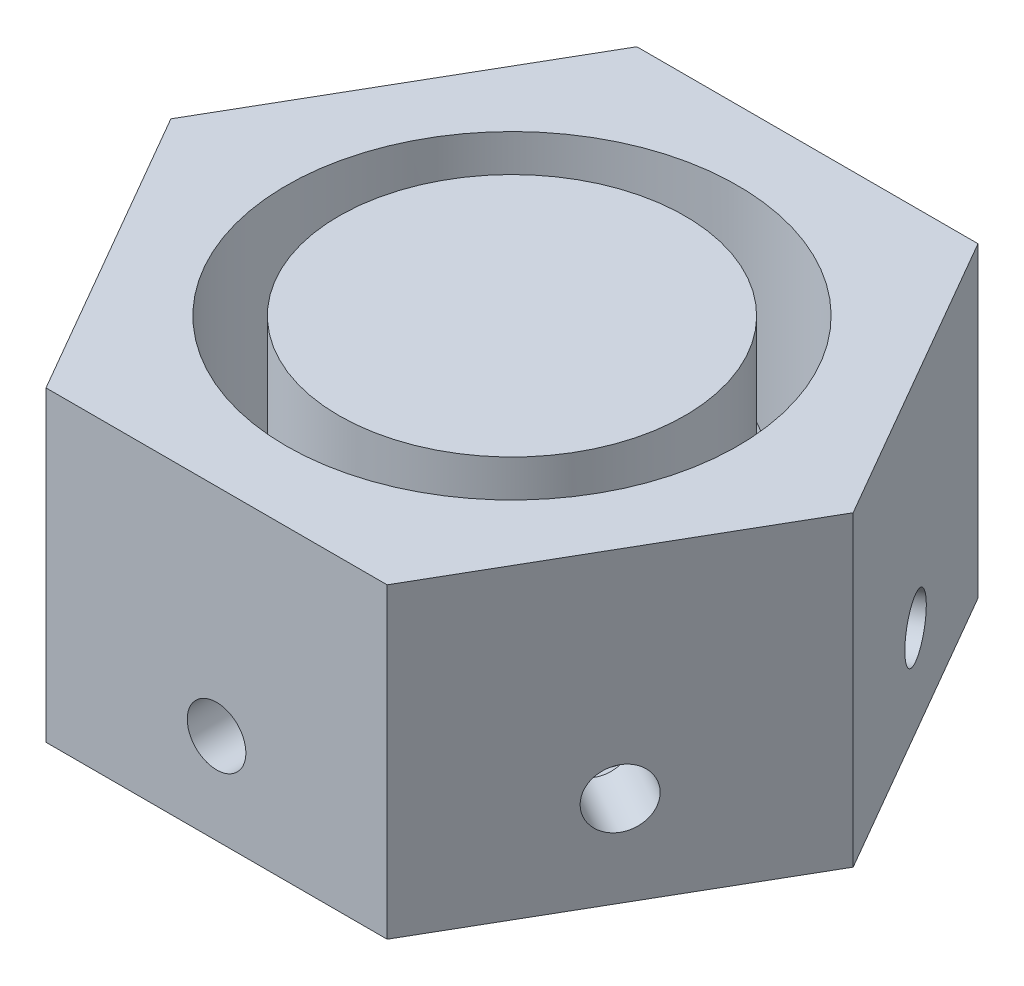
SolidWorks part; units mm, degrees
ref_plane "Front Plane" through (0, 0, 0) normal (0, 0, 1) x (1, 0, 0)
ref_plane "Top Plane" through (0, 0, 0) normal (0, 1, 0) x (1, 0, 0)
ref_plane "Right Plane" through (0, 0, 0) normal (1, 0, 0) x (0, 0, -1)
sketch "Sketch1" plane through (0, 0, 0) normal (0, 1, 0) x (1, 0, 0)
  line L1 (24.4508, 0) -> (12.2254, 21.175)
  line L2 (12.2254, 21.175) -> (-12.2254, 21.175)
  line L3 (-12.2254, 21.175) -> (-24.4508, 0)
  line L4 (-24.4508, 0) -> (-12.2254, -21.175)
  line L5 (-12.2254, -21.175) -> (12.2254, -21.175)
  line L6 (12.2254, -21.175) -> (24.4508, 0)
  circle A1 centre (0, 0) radius 21.175 construction
  circle A2 centre (0, 0) radius 12.7 construction
  circle A3 centre (0, 0) radius 15.875 construction
  circle A4 centre (0, 0) radius 12.4
  circle A5 centre (0, 0) radius 16.175
  dimension "D2" = 25.4
  dimension "D3" = 31.75
  dimension "D4" = 0.3
  dimension "D5" = 0.3
  dimension "D1" = 5
extrude "Boss-Extrude1" add sketch "Sketch1" against normal blind 2 contours L5 L6 L1 L2 L3 L4 A5 | A5 A4 | A4 region at (17.7779, 0, 10.264) region at (0, 0, 0) region at (-15.7175, 0, 0)
extrude "Boss-Extrude2" add sketch "Sketch1<3>" along normal blind 20 contours L5 L6 L1 L2 L3 L4 A5 | A4 region at (17.7779, 0, 10.264) region at (0, 0, 0)
sketch "Sketch1<3>" plane through (0, 0, 0) normal (0, 1, 0) x (1, 0, 0) same geometry as "Sketch1"
sketch "Sketch2" plane through (0, 0, 0) normal (0, 0, 1) x (1, 0, 0)
  circle A0 centre (0, 4.5) radius 2.1
  dimension "D2" = 4.2
  dimension "D1" = 4.5
extrude "Cut-Extrude1" cut sketch "Sketch2" against normal through all
pattern_circular "CirPattern1" count 6 over 360 about axis through (0, 20, 0) along (0, -1, 0) of "Cut-Extrude1"
